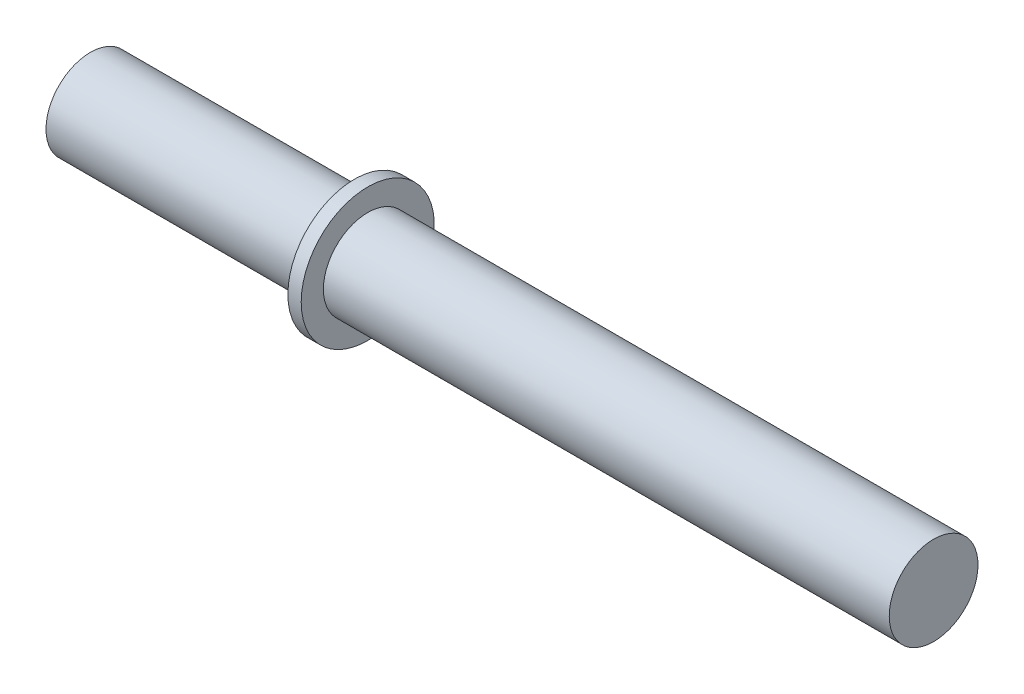
SolidWorks part; units mm, degrees
ref_plane "Alzado" through (0, 0, 0) normal (0, 0, 1) x (1, 0, 0)
ref_plane "Planta" through (0, 0, 0) normal (0, 1, 0) x (1, 0, 0)
ref_plane "Vista lateral" through (0, 0, 0) normal (1, 0, 0) x (0, 0, -1)
sketch "Croquis1" plane through (0, 0, 0) normal (1, 0, 0) x (0, 0, -1)
  circle A0 centre (0, 0) radius 10
  dimension "D1" = 20
extrude "Saliente-Extruir1" add sketch "Croquis1" along normal blind 190 from offset 8
ref_plane "Plano1" through (70.5, 0, 0) normal (-1, 0, 0) x (0, 0, 1)
sketch "Croquis2" plane through (70.5, 0, 0) normal (-1, 0, 0) x (0, 0, 1)
  circle A0 centre (0, 0) radius 15
  dimension "D1" = 30
extrude "Saliente-Extruir2" add sketch "Croquis2" along normal blind 3
